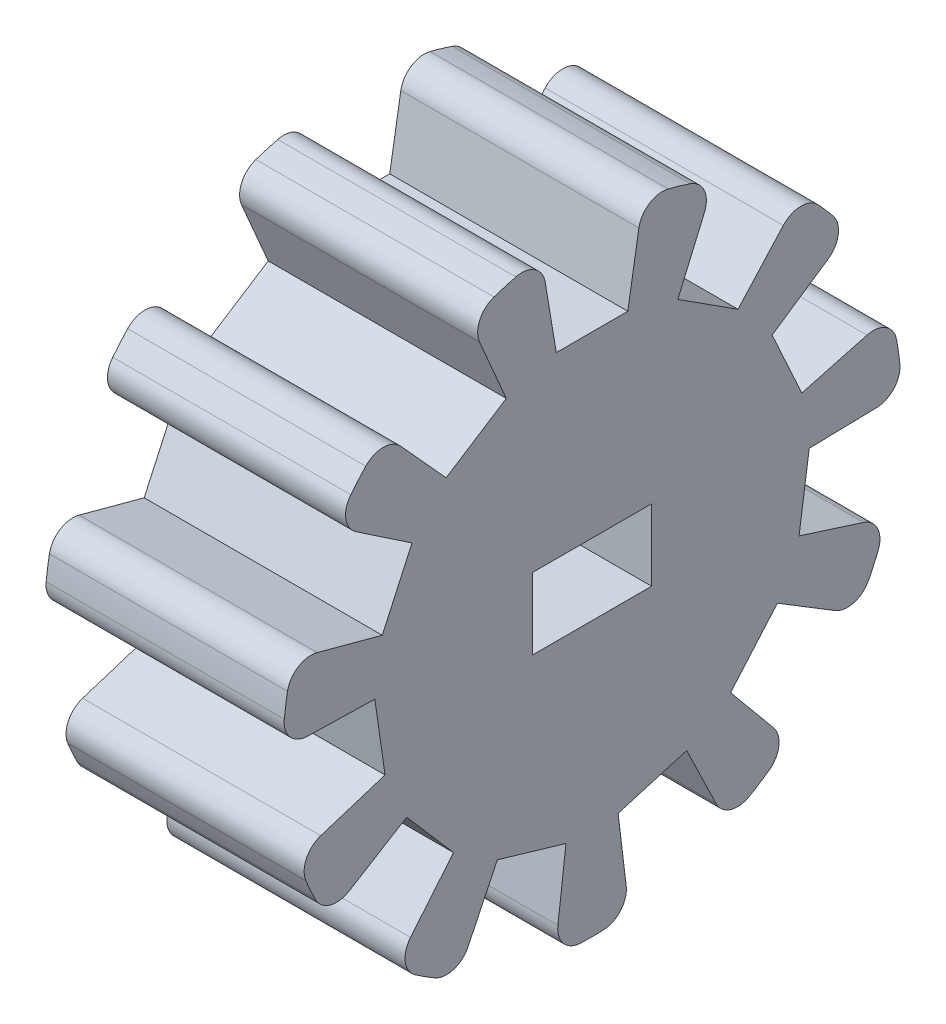
SolidWorks part; units mm, degrees
ref_plane "Front Plane" through (0, 0, 0) normal (0, 0, 1) x (1, 0, 0)
ref_plane "Top Plane" through (0, 0, 0) normal (0, 1, 0) x (1, 0, 0)
ref_plane "Right Plane" through (0, 0, 0) normal (1, 0, 0) x (0, 0, -1)
sketch "Sketch1" plane through (0, 0, 0) normal (0, 0, 1) x (1, 0, 0)
  line L0 (-10, 0) -> (-34.486, 0) construction
  line L1 (0, 0) -> (-10, 0)
  line L2 (-10, 0) -> (-10, 13)
  line L3 (0, 13) -> (0, 0)
  line L7 (-10, 13) -> (0, 13)
  dimension "D2" = 13
revolve "Revolve1" add sketch "Sketch1" angle 360 about L0
sketch "Sketch4" plane through (-10, 0, 0) normal (-1, 0, 0) x (0, 0, 1)
  line L1 (2.5, -1.5) -> (-2.5, -1.5)
  line L6 (2.5, -1.5) -> (2.5, 1.5)
  line L7 (2.5, 1.5) -> (-2.5, 1.5)
  line L8 (-2.5, -1.5) -> (-2.5, 1.5)
  line L9 (2.5, -1.5) -> (-2.5, 1.5) construction
  line L10 (2.5, 1.5) -> (-2.5, -1.5) construction
  point P0 (0, 0)
  point P3 (0, 0)
  point P8 (0, 0)
  dimension "D1" = 3
  dimension "D2" = 5
sketch "Sketch5" plane through (0, 0, 0) normal (1, 0, 0) x (0, 0, -1)
  line L0 (-2.502, 15) -> (2.502, 15)
  line L1 (-1.5018, 9) -> (1.5018, 9)
  line L2 (-2.502, 15) -> (-1.5018, 9)
  line L3 (2.502, 15) -> (1.5018, 9)
  point P6 (0, 9)
  dimension "D1" = 6
  dimension "D2" = 9
sketch "Sketch6" plane through (0, 0, 0) normal (1, 0, 0) x (0, 0, -1)
  line L0 (-1.5018, 9) -> (1.5018, 9)
  line L1 (1.5018, 9) -> (2.502, 15)
  line L2 (2.502, 15) -> (-2.502, 15)
  line L3 (-2.502, 15) -> (-1.5018, 9)
extrude "Cut-Extrude1" cut sketch "Sketch6" against normal blind 10
sketch "Sketch7" plane through (0, 0, 0) normal (1, 0, 0) x (0, 0, -1)
  line L0 (-2.5, 1.5) -> (2.5, 1.5)
  line L1 (2.5, 1.5) -> (2.5, -1.5)
  line L2 (2.5, -1.5) -> (-2.5, -1.5)
  line L3 (-2.5, -1.5) -> (-2.5, 1.5)
extrude "Cut-Extrude2" cut sketch "Sketch7" against normal blind 10
fillet "Fillet1" radius 1 2 edges at (-5, 12.8228, -2.1391) (-5, 12.8228, 2.1391)
pattern_circular "CirPattern1" count 11 over 360 about axis through (-10, 0, 0) along (1, 0, 0) of "Fillet1", "Cut-Extrude1" reverse direction yes
